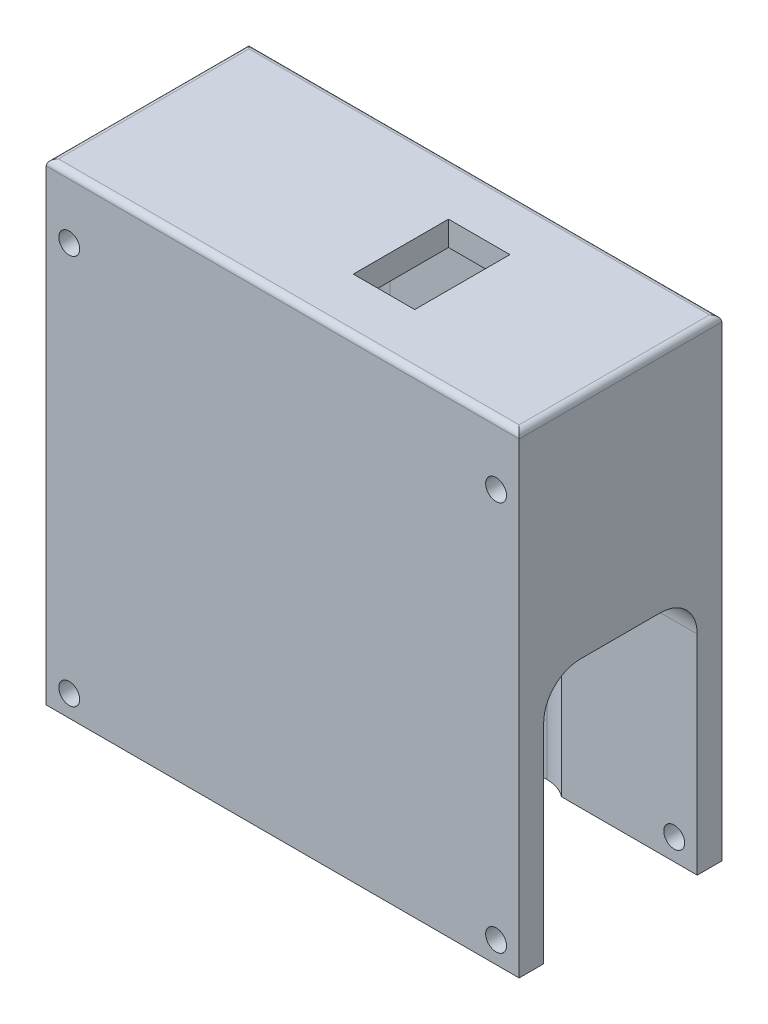
SolidWorks part; units mm, degrees
material "ABS"
ref_plane "Front" through (0, 0, 0) normal (0, 0, 1) x (1, 0, 0)
ref_plane "Top" through (0, 0, 0) normal (0, 1, 0) x (1, 0, 0)
ref_plane "Right" through (0, 0, 0) normal (1, 0, 0) x (0, 0, -1)
sketch "ｽｹｯﾁ1" plane through (0, 0, 0) normal (0, 1, 0) x (1, 0, 0)
  line L1 (38.5, 16.5) -> (-38.5, 16.5)
  line L2 (38.5, 16.5) -> (38.5, -16.5)
  line L3 (38.5, -16.5) -> (-38.5, -16.5)
  line L4 (-38.5, 16.5) -> (-38.5, -16.5)
  line L5 (38.5, 16.5) -> (-38.5, -16.5) construction
  line L6 (38.5, -16.5) -> (-38.5, 16.5) construction
  point P0 (0, 0)
  dimension "D1" = 33
  dimension "D2" = 77
extrude "ﾎﾞｽ - 押し出し1" add sketch "ｽｹｯﾁ1" along normal blind 77
sketch "ｽｹｯﾁ2" plane through (0, 0, 0) normal (0, -1, 0) x (1, 0, 0)
  line L1 (12.75, 13.75) -> (-12.75, 13.75)
  line L2 (18.75, 7.75) -> (18.75, -7.75)
  line L3 (12.75, -13.75) -> (-12.75, -13.75)
  line L4 (-18.75, 7.75) -> (-18.75, -7.75)
  line L5 (18.75, 13.75) -> (-18.75, -13.75) construction
  line L6 (18.75, -13.75) -> (-18.75, 13.75) construction
  arc A0 (12.75, 13.75) -> (18.75, 7.75) centre (12.75, 7.75) cw
  arc A1 (18.75, -7.75) -> (12.75, -13.75) centre (12.75, -7.75) cw
  arc A2 (-12.75, -13.75) -> (-18.75, -7.75) centre (-12.75, -7.75) cw
  arc A3 (-18.75, 7.75) -> (-12.75, 13.75) centre (-12.75, 7.75) cw
  point P0 (0, 0)
  dimension "D3" = 6
  dimension "D1" = 37.5
  dimension "D2" = 27.5
extrude "ｶｯﾄ - 押し出し1" cut sketch "ｽｹｯﾁ2" against normal blind 73
sketch "ｽｹｯﾁ3" plane through (0, 0, 16.5) normal (0, 0, 1) x (1, 0, 0)
  line L0 (-38.5, 0) -> (38.5, 0) construction
  line L1 (-38.5, 77) -> (-38.5, 0) construction
  line L2 (-38.5, 77) -> (38.5, 77) construction
  line L3 (38.5, 77) -> (38.5, 0) construction
  circle A0 centre (34.75, 3.5) radius 1.7
  circle A1 centre (34.75, 67) radius 1.7
  circle A2 centre (-34.75, 67) radius 1.7
  circle A3 centre (-34.75, 3.5) radius 1.7
  dimension "D1" = 3.4
  dimension "D2" = 3.5
  dimension "D3" = 3.75
  dimension "D4" = 10
  dimension "D5" = 3.75
extrude "ｶｯﾄ - 押し出し2" cut sketch "ｽｹｯﾁ3" against normal through all
sketch "ｽｹｯﾁ4" plane through (-38.5, 0, 0) normal (-1, 0, 0) x (0, 0, 1)
  line L0 (-16.5, 0) -> (16.5, 0) construction
  line L1 (6.5, 40) -> (-6.5, 40)
  line L2 (12.5, 34) -> (12.5, 0)
  line L3 (12.5, 0) -> (-12.5, 0)
  line L4 (-12.5, 34) -> (-12.5, 0)
  line L5 (12.5, 40) -> (-12.5, 0) construction
  line L6 (12.5, 0) -> (-12.5, 40) construction
  arc A0 (6.5, 40) -> (12.5, 34) centre (6.5, 34) cw
  arc A1 (-6.5, 40) -> (-12.5, 34) centre (-6.5, 34) ccw
  point P0 (0, 20)
  dimension "D4" = 6
  dimension "D1" = 25
  dimension "D2" = 40
  dimension "D3" = 0
extrude "ｶｯﾄ - 押し出し3" cut sketch "ｽｹｯﾁ4" against normal through all
sketch "ｽｹｯﾁ5" plane through (0, 73, 0) normal (0, -1, 0) x (1, 0, 0)
  line L0 (18.75, -7.75) -> (18.75, 7.75) construction
  line L1 (2.75, -7.75) -> (12.75, -7.75)
  line L2 (2.75, -7.75) -> (2.75, 7.75)
  line L3 (2.75, 7.75) -> (12.75, 7.75)
  line L4 (12.75, -7.75) -> (12.75, 7.75)
  line L5 (2.75, -7.75) -> (12.75, 7.75) construction
  line L6 (2.75, 7.75) -> (12.75, -7.75) construction
  line L7 (-12.75, -13.75) -> (12.75, -13.75) construction
  line L8 (12.75, 13.75) -> (-12.75, 13.75) construction
  point P0 (7.75, 0)
  dimension "D1" = 6
  dimension "D2" = 6
  dimension "D3" = 6
  dimension "D4" = 10
extrude "ｶｯﾄ - 押し出し4" cut sketch "ｽｹｯﾁ5" against normal through all
fillet "ﾌｨﾚｯﾄ1" radius 1 4 edges at (0, 77, 16.5) (-38.5, 77, 0) (0, 77, -16.5) (38.5, 77, 0)
